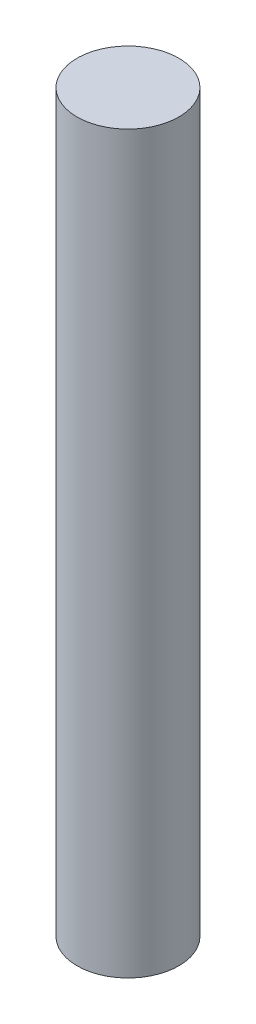
SolidWorks part; units mm, degrees
ref_plane "Front Plane" through (0, 0, 0) normal (0, 0, 1) x (1, 0, 0)
ref_plane "Top Plane" through (0, 0, 0) normal (0, 1, 0) x (1, 0, 0)
ref_plane "Right Plane" through (0, 0, 0) normal (1, 0, 0) x (0, 0, -1)
sketch "Sketch1" plane through (0, 0, 0) normal (0, 1, 0) x (1, 0, 0)
  circle A0 centre (0, 0) radius 25
  dimension "D1" = 50
extrude "Boss-Extrude1" add sketch "Sketch1" against normal blind 361
